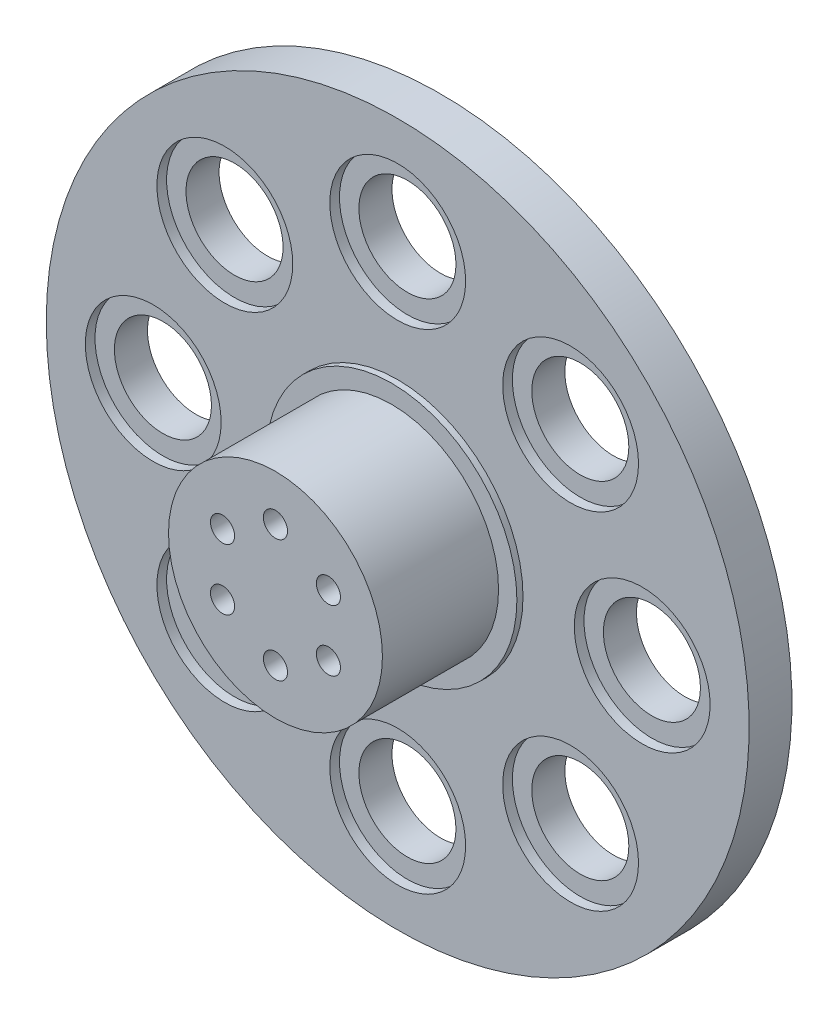
SolidWorks part; units mm, degrees
material "PETG"
ref_plane "Front Plane" through (0, 0, 0) normal (0, 0, 1) x (1, 0, 0)
ref_plane "Top Plane" through (0, 0, 0) normal (0, 1, 0) x (1, 0, 0)
ref_plane "Right Plane" through (0, 0, 0) normal (1, 0, 0) x (0, 0, -1)
sketch "Sketch1" plane through (0, 0, 0) normal (0, 0, 1) x (1, 0, 0)
  circle A0 centre (0, 0) radius 17.5
  dimension "D1" = 35
extrude "Boss-Extrude1" add sketch "Sketch1" along normal blind 19
sketch "Sketch7" plane through (0, 0, 0) normal (0, 0, -1) x (-1, 0, 0)
  circle A0 centre (0, 0) radius 20.5
  dimension "D1" = 41
extrude "Boss-Extrude3" add sketch "Sketch7" along normal blind 1
sketch "Sketch3" plane through (0, 0, -1) normal (0, 0, -1) x (-1, 0, 0)
  circle A0 centre (0, 0) radius 57.5
  dimension "D1" = 115
extrude "Boss-Extrude2" add sketch "Sketch3" along normal blind 7
sketch "Sketch4" plane through (0, 0, -8) normal (0, 0, -1) x (-1, 0, 0)
  circle A0 centre (0, 0) radius 11
  dimension "D1" = 22
extrude "Cut-Extrude1" cut sketch "Sketch4" against normal blind 7
sketch "Sketch5" plane through (0, 0, -1) normal (0, 0, -1) x (-1, 0, 0)
  circle A0 centre (0, 0) radius 7.5
  dimension "D1" = 15
extrude "Cut-Extrude2" cut sketch "Sketch5" against normal blind 0.5
sketch "Sketch6" plane through (0, 0, 19) normal (0, 0, 1) x (1, 0, 0)
  circle A0 centre (0, 10) radius 1.975
  dimension "D1" = 3.95
  dimension "D2" = 10
extrude "Cut-Extrude3" cut sketch "Sketch6" against normal blind 10
pattern_circular "CirPattern1" count 6 over 360 about axis through (0, 0, 19) along (0, 0, 1) of "Cut-Extrude3"
sketch "Sketch8" plane through (0, 0, -1) normal (0, 0, 1) x (1, 0, 0)
  circle A0 centre (0, 0) radius 40 construction
  circle A1 centre (-40, 0) radius 7.94
  circle A2 centre (-28.2843, 28.2843) radius 7.94
  circle A3 centre (0, 40) radius 7.94
  circle A4 centre (28.2843, 28.2843) radius 7.94
  circle A5 centre (40, 0) radius 7.94
  circle A6 centre (28.2843, -28.2843) radius 7.94
  circle A7 centre (0, -40) radius 7.94
  circle A8 centre (-28.2843, -28.2843) radius 7.94
  dimension "D1" = 80
  dimension "D2" = 15.88
  dimension "D3" = 8
extrude "Cut-Extrude4" cut sketch "Sketch8" against normal through all
sketch "Sketch9" plane through (0, 0, -1) normal (0, 0, 1) x (1, 0, 0)
  line L0 (0, 0) -> (0, 40) construction
  circle A0 centre (0, 40) radius 11.1125
  circle A1 centre (0, 40) radius 7.94 construction
  circle A2 centre (28.2843, 28.2843) radius 11.1125
  circle A3 centre (40, 0) radius 11.1125
  circle A4 centre (28.2843, -28.2843) radius 11.1125
  circle A5 centre (0, -40) radius 11.1125
  circle A6 centre (-28.2843, -28.2843) radius 11.1125
  circle A7 centre (-40, 0) radius 11.1125
  circle A8 centre (-28.2843, 28.2843) radius 11.1125
  point P17 (0, 0)
  dimension "D1" = 22.225
  dimension "D2" = 8
extrude "Cut-Extrude5" cut sketch "Sketch9" against normal blind 1.5875
chamfer "Chamfer1" distance 1 angle 45 1 edges at (-11, 0, -8)
equation "\"N\"= 21"
equation "\"R\"= 65mm"
equation "\"E\" = ROUND(\"R\" / \"N\" * 0.7, 2)"
equation "\"R_r\" = ( 1in / 2 ) / 2"
equation "\"D_p\" = 8cm"
equation "\"D1@Sketch8\"=\"D_p\""
equation "\"N_p\" = 8"
equation "\"D3@Sketch8\"=\"N_p\""
